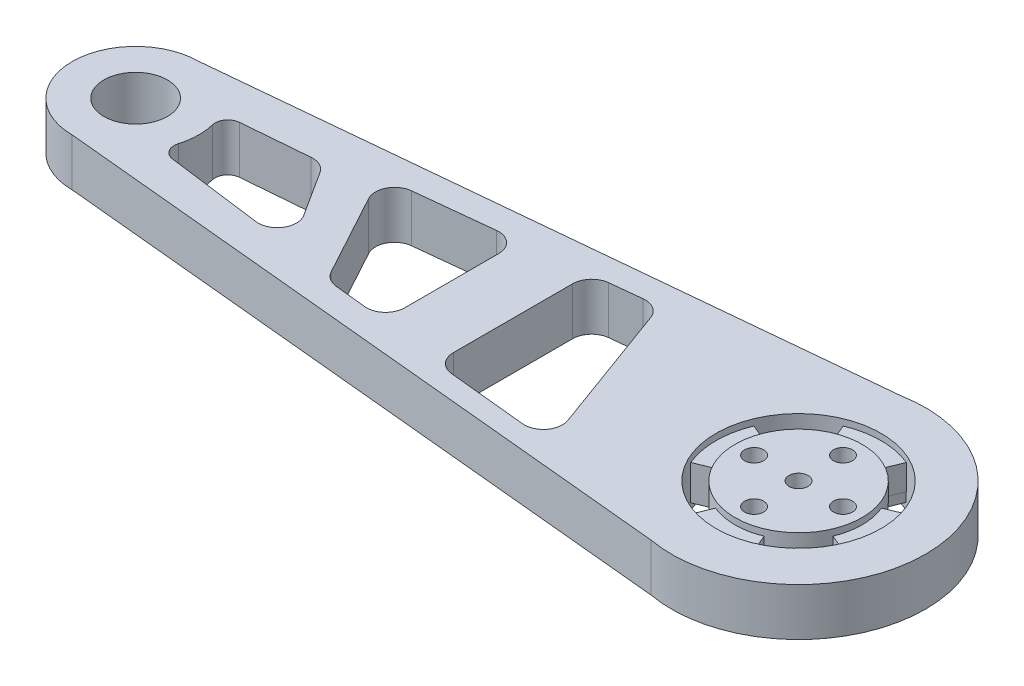
SolidWorks part; units mm, degrees
ref_plane "前视基准面" through (0, 0, 0) normal (0, 0, 1) x (1, 0, 0)
ref_plane "上视基准面" through (0, 0, 0) normal (0, 1, 0) x (1, 0, 0)
ref_plane "右视基准面" through (0, 0, 0) normal (1, 0, 0) x (0, 0, -1)
sketch "草图1" plane through (0, 0, 0) normal (1, 0, 0) x (0, 0, -1)
  line L11 (10, 0) -> (10, 3.75)
  line L12 (10, 3.75) -> (-10, 3.75)
  line L13 (-10, 3.75) -> (-10, -3.75)
  line L14 (-10, -3.75) -> (10, -3.75)
  line L15 (10, -3.75) -> (10, 0)
  dimension "D2" = 3.75
  dimension "D4" = 7.5
extrude "凸台-拉伸1" add sketch "草图1" along normal blind 47 and the other way blind 57
sketch "草图2" plane through (0, 0, 0) normal (0, 1, 0) x (1, 0, 0)
  circle A6 centre (47.398, 0) radius 20
  dimension "D1" = 40
extrude "凸台-拉伸2" add sketch "草图2" along normal blind 3.75 and the other way blind 3.75
sketch "草图3" plane through (0, 0, 0) normal (0, 1, 0) x (1, 0, 0)
  line L0 (47.398, 22.3482) -> (47.398, -22.3482) construction
  line L1 (32.2189, 0) -> (62.577, 0) construction
  line L2 (59.4084, -4.9749) -> (56.6368, -3.8268)
  line L3 (52.3728, -12.0104) -> (51.2248, -9.2388)
  line L4 (42.4231, -12.0104) -> (43.5711, -9.2388)
  line L5 (52.3728, 12.0104) -> (51.2248, 9.2388)
  line L6 (59.4084, 4.9749) -> (56.6368, 3.8268)
  line L7 (35.3875, -4.9749) -> (38.1592, -3.8268)
  line L8 (35.3875, 4.9749) -> (38.1592, 3.8268)
  line L9 (42.4231, 12.0104) -> (43.5711, 9.2388)
  circle A0 centre (47.398, 0) radius 10
  circle A1 centre (47.398, 0) radius 13
  circle A2 centre (47.398, 7) radius 1.5
  circle A3 centre (47.398, 0) radius 1.5
  circle A4 centre (54.398, 0) radius 1.5
  circle A5 centre (47.398, -7) radius 1.5
  circle A6 centre (40.398, 0) radius 1.5
  point P19 (47.398, 0)
  point P39 (47.398, 0)
  dimension "D1" = 20
  dimension "D2" = 26
  dimension "D4" = 3
  dimension "D5" = 3
  dimension "D3" = 7
extrude "切除-拉伸1" cut sketch "草图3" against normal blind 3.75 and the other way blind 3.75 contours L6 A1 L5 A0 | L9 A1 L8 A0 | A5 | L3 A1 L2 A0 | L7 A1 L4 A0 | A6 | A2 | A4 | A3 region at (55.3672, 0, 7.9693) region at (39.4287, 0, 7.9693) region at (55.3672, 0, -7.9693) region at (39.4287, 0, -7.9693) region at (47.398, 0, -7) region at (47.398, 0, 7) region at (40.398, 0, 0)
sketch "草图4" plane through (0, 3.75, 0) normal (0, 1, 0) x (1, 0, 0)
  line L2 (43.5711, 9.2388) -> (42.4231, 12.0104)
  line L3 (51.2248, 9.2388) -> (52.3728, 12.0104)
  line L4 (56.6368, 3.8268) -> (59.4084, 4.9749)
  line L5 (56.6368, -3.8268) -> (59.4084, -4.9749)
  line L6 (51.2248, -9.2388) -> (52.3728, -12.0104)
  line L7 (43.5711, -9.2388) -> (42.4231, -12.0104)
  line L8 (38.1592, -3.8268) -> (35.3875, -4.9749)
  line L9 (38.1592, 3.8268) -> (35.3875, 4.9749)
  arc A2 (42.4231, 12.0104) -> (52.3728, 12.0104) centre (47.398, 0) cw
  arc A3 (51.2248, 9.2388) -> (43.5711, 9.2388) centre (47.398, 0) ccw
  arc A4 (59.4084, 4.9749) -> (59.4084, -4.9749) centre (47.398, 0) cw
  arc A5 (56.6368, -3.8268) -> (56.6368, 3.8268) centre (47.398, 0) ccw
  arc A6 (52.3728, -12.0104) -> (42.4231, -12.0104) centre (47.398, 0) cw
  arc A7 (43.5711, -9.2388) -> (51.2248, -9.2388) centre (47.398, 0) ccw
  arc A8 (35.3875, -4.9749) -> (35.3875, 4.9749) centre (47.398, 0) cw
  arc A9 (38.1592, 3.8268) -> (38.1592, -3.8268) centre (47.398, 0) ccw
  point P29 (47.398, 0)
extrude "切除-拉伸2" cut sketch "草图4" against normal blind 1
sketch "草图5" plane through (0, -3.75, 0) normal (0, -1, 0) x (1, 0, 0)
  circle A2 centre (47.398, 0) radius 10
  arc A3 (52.3728, 12.0104) -> (42.4231, 12.0104) centre (47.398, 0) ccw
  arc A4 (59.4084, -4.9749) -> (59.4084, 4.9749) centre (47.398, 0) ccw
  arc A5 (42.4231, -12.0104) -> (52.3728, -12.0104) centre (47.398, 0) ccw
  arc A6 (35.3875, 4.9749) -> (35.3875, -4.9749) centre (47.398, 0) ccw
  point P20 (47.398, 0)
  line M4 (42.4231, 12.0104) -> (43.5711, 9.2388)
  arc M5 (43.5711, 9.2388) -> (38.1592, 3.8268) centre (47.398, 0) ccw
  line M6 (38.1592, 3.8268) -> (35.3875, 4.9749)
  circle M7 centre (40.398, 0) radius 1.5
  line M8 (56.6368, -3.8268) -> (59.4084, -4.9749)
  line M10 (52.3728, -12.0104) -> (51.2248, -9.2388)
  arc M11 (51.2248, -9.2388) -> (56.6368, -3.8268) centre (47.398, 0) ccw
  circle M12 centre (47.398, 0) radius 1.5
  line M18 (35.3875, -4.9749) -> (38.1592, -3.8268)
  arc M19 (38.1592, -3.8268) -> (43.5711, -9.2388) centre (47.398, 0) ccw
  line M20 (43.5711, -9.2388) -> (42.4231, -12.0104)
  circle M21 centre (54.398, 0) radius 1.5
  line M23 (59.4084, 4.9749) -> (56.6368, 3.8268)
  arc M24 (56.6368, 3.8268) -> (51.2248, 9.2388) centre (47.398, 0) ccw
  line M25 (51.2248, 9.2388) -> (52.3728, 12.0104)
  circle M26 centre (47.398, -7) radius 1.5
  circle M27 centre (47.398, 7) radius 1.5
extrude "切除-拉伸3" cut sketch "草图5" against normal blind 2.5 contours A3 A2 M25 M4 | A2 M11 M24 M5 M19 M7 M26 M27 M21 M12 | A4 A2 M8 M23 | A6 A2 M6 M18 | A5 A2 M20 M10 region at (56.9284, -3.75, -1.8957) region at (58.6682, -3.75, 0) region at (47.398, -3.75, 11.2703) region at (47.398, -3.75, -11.2703) region at (36.1277, -3.75, 0)
sketch "草图6" plane through (0, -1.25, 0) normal (0, -1, 0) x (1, 0, 0)
  line L0 (59.4408, 4.896) -> (56.6617, 3.7662)
  line L1 (59.4084, -4.9749) -> (56.6368, -3.8268)
  line L2 (51.2248, 9.2388) -> (52.3728, 12.0104) construction
  line L3 (42.502, 12.0428) -> (43.6318, 9.2637)
  line L4 (52.3728, 12.0104) -> (51.2248, 9.2388)
  line L5 (52.294, -12.0428) -> (51.1641, -9.2637)
  line L6 (42.4231, -12.0104) -> (43.5711, -9.2388)
  line L7 (35.3552, -4.896) -> (38.1343, -3.7662)
  line L8 (35.3875, 4.9749) -> (38.1592, 3.8268)
  arc A2 (52.3728, 12.0104) -> (42.502, 12.0428) centre (47.398, 0) ccw
  arc A3 (51.2248, 9.2388) -> (43.6318, 9.2637) centre (47.398, 0) ccw
  arc A4 (59.4084, -4.9749) -> (59.4408, 4.896) centre (47.398, 0) ccw
  arc A5 (56.6368, -3.8268) -> (56.6617, 3.7662) centre (47.398, 0) ccw
  arc A6 (42.4231, -12.0104) -> (52.294, -12.0428) centre (47.398, 0) ccw
  arc A7 (43.5711, -9.2388) -> (51.1641, -9.2637) centre (47.398, 0) ccw
  arc A8 (35.3875, 4.9749) -> (35.3552, -4.896) centre (47.398, 0) ccw
  arc A9 (38.1592, 3.8268) -> (38.1343, -3.7662) centre (47.398, 0) ccw
  point P24 (47.398, 0)
extrude "凸台-拉伸3" add sketch "草图6" along normal blind 1.5
sketch "草图7" plane through (0, 0, 0) normal (0, 1, 0) x (1, 0, 0)
  line L0 (-57, 10) -> (-57, -10) construction
  circle A1 centre (-57, 0) radius 5
  circle A2 centre (-57, 0) radius 10
  dimension "D1" = 20
  dimension "D2" = 10
extrude "凸台-拉伸4" add sketch "草图7" along normal blind 3.75 and the other way blind 3.75
sketch "草图8" plane through (0, 0, 0) normal (0, 1, 0) x (1, 0, 0)
  line L0 (-57, 5) -> (-57, -5) construction
  circle A0 centre (-57, 0) radius 5
extrude "切除-拉伸4" cut sketch "草图8" against normal blind 3.75 and the other way blind 3.75
sketch "草图9" plane through (0, 0, 0) normal (0, 1, 0) x (1, 0, 0)
  line L0 (-57, 10) -> (43.8139, 19.6762)
  line L1 (-61.0221, 0) -> (61.0221, 0) construction
  line L2 (-57, -10) -> (43.8139, -19.6762)
  line L3 (-57, 10) -> (30.0774, 10)
  line L4 (-57, -10) -> (30.0774, -10)
  arc A0 (30.0774, -10) -> (30.0774, 10) centre (47.398, 0) ccw construction
  arc A2 (30.0774, 10) -> (43.8139, 19.6762) centre (47.398, 0) cw
  arc A3 (43.8139, -19.6762) -> (30.0774, -10) centre (47.398, 0) cw
extrude "凸台-拉伸5" add sketch "草图9" along normal blind 3.75 and the other way blind 3.75
sketch "草图10" plane through (0, 0, 0) normal (0, 1, 0) x (1, 0, 0)
  line L9 (-17.9209, -8.2947) -> (-24.9712, 4.6786)
  line L10 (-22.6531, 9.0942) -> (-10.543, 10.3845)
  line L11 (-15.6028, -9.8454) -> (-10.543, -10.3845)
  line L12 (-7.2251, -7.4014) -> (-7.2251, 7.4014)
  line L13 (-27.7761, -2.7605) -> (-32.3464, 4.3826)
  line L14 (-35.1235, 5.7553) -> (-45.5428, 4.8835)
  line L15 (5.4183, -12.6818) -> (17.8597, -13.9332)
  line L16 (5.4007, 12.0833) -> (10.3306, 12.6086)
  line L17 (13.4665, 10.6543) -> (20.978, -9.9194)
  line L18 (2.7186, 9.1002) -> (2.7186, -9.6969)
  line L19 (-30.6885, -7.3525) -> (-45.776, -5.398)
  arc A6 (-24.9712, 4.6786) -> (-22.6531, 9.0942) centre (-22.3353, 6.1111) cw
  arc A7 (-17.9209, -8.2947) -> (-15.6028, -9.8454) centre (-15.285, -6.8623) ccw
  arc A8 (-7.2251, 7.4014) -> (-10.543, 10.3845) centre (-10.2251, 7.4014) ccw
  arc A9 (-10.543, -10.3845) -> (-7.2251, -7.4014) centre (-10.2251, -7.4014) ccw
  arc A10 (2.7186, 9.1002) -> (5.4007, 12.0833) centre (5.7186, 9.1002) cw
  arc A11 (5.4183, -12.6818) -> (2.7186, -9.6969) centre (5.7186, -9.6969) cw
  arc A12 (13.4665, 10.6543) -> (10.3306, 12.6086) centre (10.6484, 9.6255) ccw
  arc A13 (17.8597, -13.9332) -> (20.978, -9.9194) centre (18.1599, -10.9483) ccw
  arc A27 (-47.317, 2.4079) -> (-47.4361, -2.8444) centre (-57, 0) cw
  arc A28 (-47.317, 2.4079) -> (-45.5428, 4.8835) centre (-45.3761, 2.8905) cw
  arc A29 (-45.776, -5.398) -> (-47.4361, -2.8444) centre (-45.5191, -3.4145) cw
  arc A30 (-32.3464, 4.3826) -> (-35.1235, 5.7553) centre (-34.8734, 2.7657) ccw
  arc A31 (-30.6885, -7.3525) -> (-27.7761, -2.7605) centre (-30.3031, -4.3773) ccw
  point P8 (-37.0563, 7.5595)
  point P28 (-27.1126, -8.619)
  point P31 (-27.1126, 8.619)
  point P34 (-17.1689, -9.6785)
  point P37 (-7.2251, 10.738)
  point P40 (-7.2251, -10.738)
  point P43 (2.7186, 11.7975)
  point P46 (2.7186, -12.4103)
  point P49 (12.6623, 12.857)
  point P52 (22.6182, -14.4118)
  point P61 (-47, 6.5)
  point P64 (-47, -6.5)
  dimension "D13" = 2
  dimension "D14" = 2
  dimension "D15" = 3
  dimension "D16" = 3
  dimension "D17" = 3
  dimension "D18" = 3
  dimension "D19" = 3
  dimension "D20" = 3
  dimension "D21" = 3
  dimension "D25" = 3
  dimension "D26" = 3
  dimension "D2" = 10
  dimension "D3" = 20
  dimension "D4" = 10
  dimension "D5" = 10
  dimension "D6" = 20
  dimension "D7" = 10
  dimension "D8" = 10
  dimension "D9" = 20
  dimension "D10" = 10
extrude "切除-拉伸5" cut sketch "草图10" against normal blind 3.75 and the other way blind 3.75
